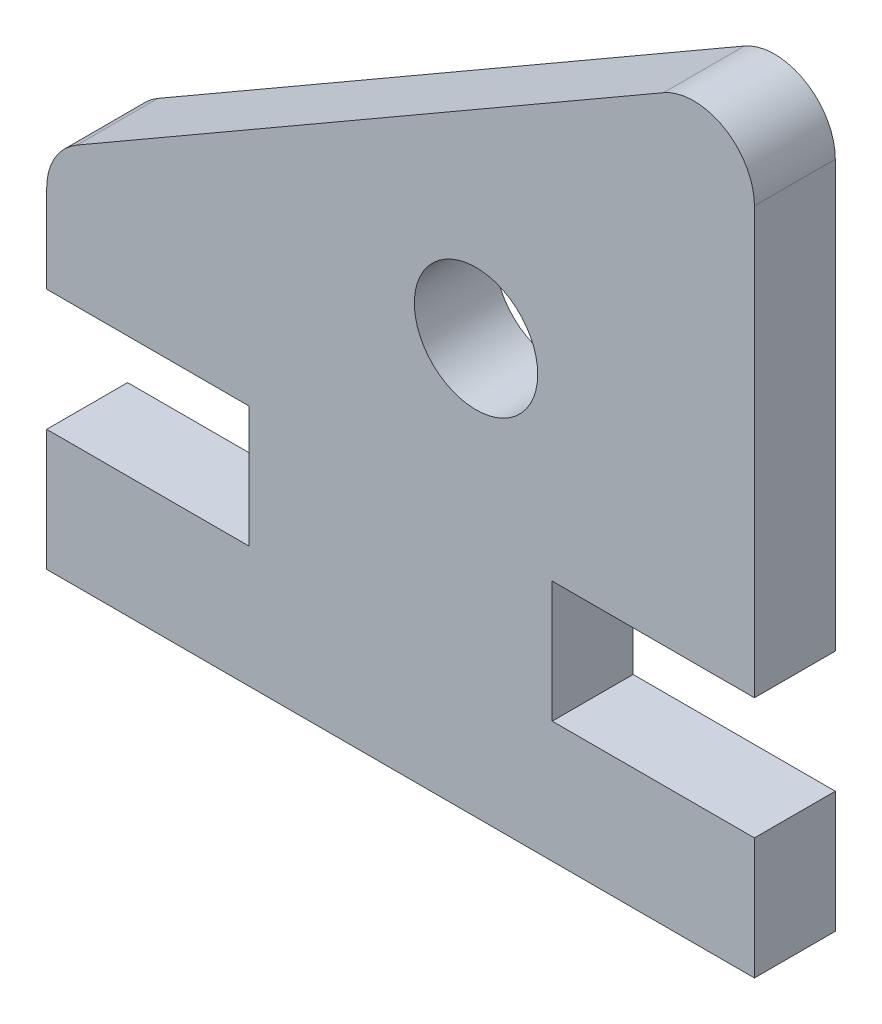
SolidWorks part; units mm, degrees
material "Policarbonato"
ref_plane "Plano frontal" through (0, 0, 0) normal (0, 0, 1) x (1, 0, 0)
ref_plane "Plano superior" through (0, 0, 0) normal (0, 1, 0) x (1, 0, 0)
ref_plane "Plano direito" through (0, 0, 0) normal (1, 0, 0) x (0, 0, -1)
sketch "Esboço1" plane through (0, 0, 0) normal (0, 0, 1) x (1, 0, 0)
  line L0 (-35, 18.0566) -> (0, 38.2639)
  line L1 (0, 38.2639) -> (0, 0)
  line L2 (0, 0) -> (-35, 0)
  line L3 (-35, 0) -> (-35, 18.0566)
  line L5 (-25, 6) -> (-35, 6)
  line L6 (-25, 6) -> (-25, 12)
  line L7 (-25, 12) -> (-35, 12)
  line L8 (-35, 6) -> (-35, 12)
  line L9 (-25, 6) -> (-35, 12) construction
  line L10 (-25, 12) -> (-35, 6) construction
  line L11 (0, 6) -> (-10, 6)
  line L12 (0, 6) -> (0, 12)
  line L13 (0, 12) -> (-10, 12)
  line L14 (-10, 6) -> (-10, 12)
  line L15 (0, 6) -> (-10, 12) construction
  line L16 (0, 12) -> (-10, 6) construction
  circle A0 centre (-13.7679, 20.5) radius 3.05
  circle A1 centre (-13.7679, 20.5) radius 8.5 construction
  point P2 (-5, 9)
  point P8 (-30, 9)
  dimension "D10" = 6.1
  dimension "D11" = 17
  dimension "D1" = 30
  dimension "D2" = 18.0566
  dimension "D3" = 35
  dimension "D5" = 10
  dimension "D6" = 6
  dimension "D9" = 6
extrude "Ressalto-extrusão1" add sketch "Esboço1" along normal blind 4 contours L11 L14 L13 L1 L0 L3 L7 L6 L5 L2 A0 region at (-15.164, 15.2967, 0)
fillet "Filete1" radius 3 2 edges at (-35, 18.0566, 2) (0, 38.2639, 2)
